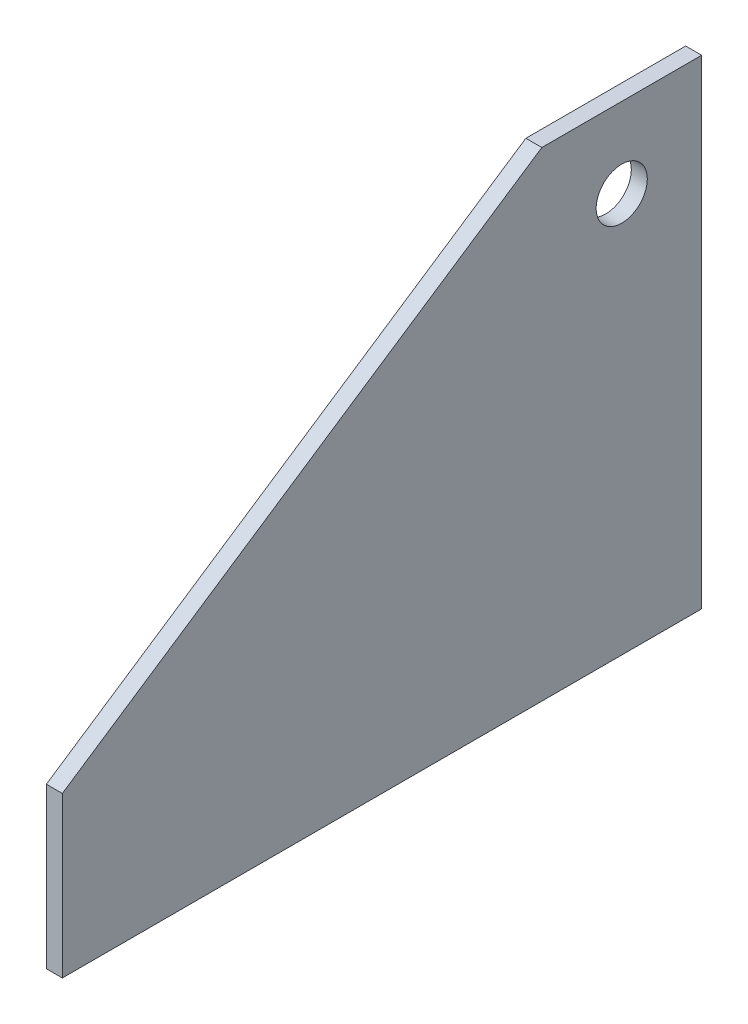
SolidWorks part; units mm, degrees
ref_plane "Alzado" through (0, 0, 0) normal (0, 0, 1) x (1, 0, 0)
ref_plane "Planta" through (0, 0, 0) normal (0, 1, 0) x (1, 0, 0)
ref_plane "Vista lateral" through (0, 0, 0) normal (1, 0, 0) x (0, 0, -1)
sketch "Croquis1" plane through (0, 0, 0) normal (1, 0, 0) x (0, 0, -1)
  line L0 (50, 75) -> (-100, -25)
  line L1 (-100, -75) -> (100, -75)
  line L2 (-100, -75) -> (-100, -25)
  line L3 (50, 75) -> (100, 75)
  line L4 (100, -75) -> (100, 75)
  line L5 (100, 0) -> (-62.5, 0) construction
  line L6 (75, 75) -> (75, -75) construction
  circle A0 centre (75, 50) radius 8
  point P0 (0, 0)
  dimension "D6" = 16
  dimension "D1" = 150
  dimension "D2" = 200
  dimension "D3" = 50
  dimension "D4" = 50
  dimension "D5" = 50
extrude "Saliente-Extruir1" add sketch "Croquis1" along normal blind 5
